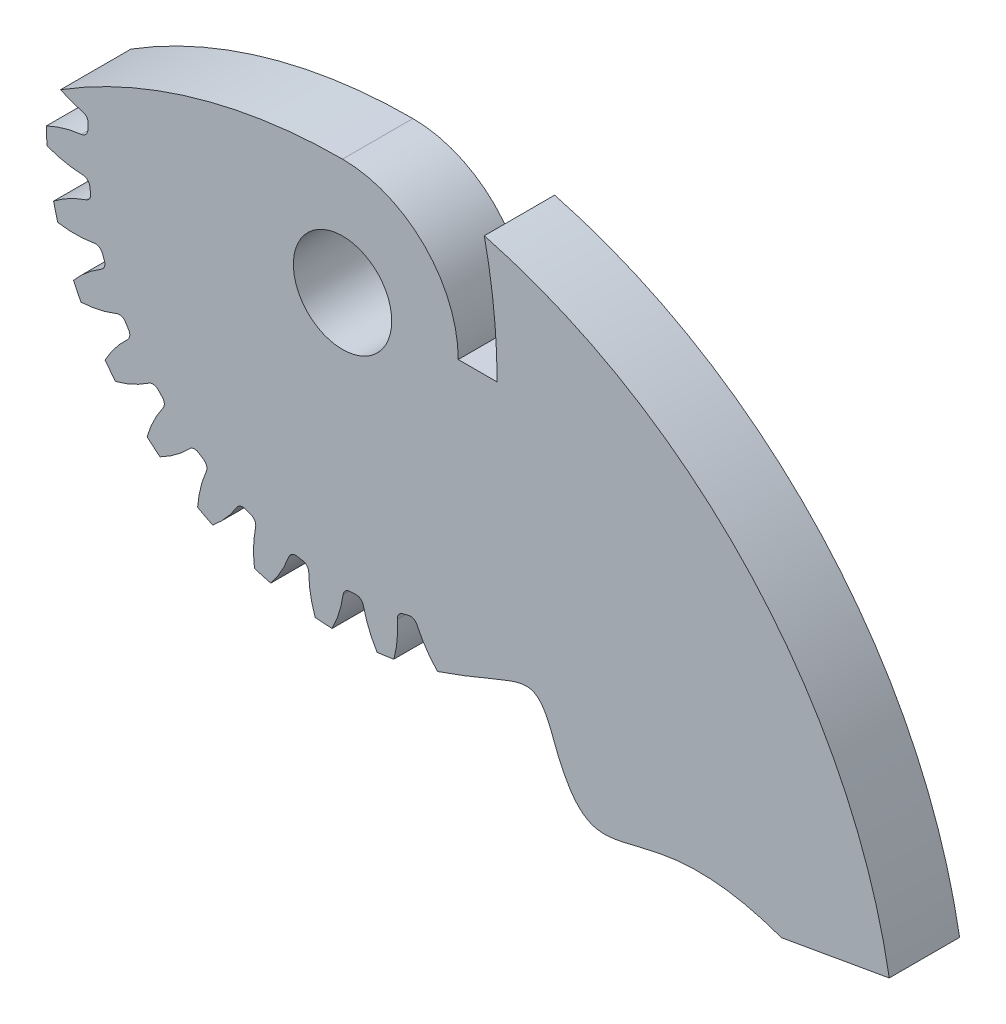
SolidWorks part; units mm, degrees
material "ABS"
ref_plane "Front" through (0, 0, 0) normal (0, 0, 1) x (1, 0, 0)
ref_plane "Top" through (0, 0, 0) normal (0, 1, 0) x (1, 0, 0)
ref_plane "Right" through (0, 0, 0) normal (1, 0, 0) x (0, 0, -1)
sketch "Sketch3" plane through (0, 0, 0) normal (0, 0, 1) x (1, 0, 0)
  circle A0 centre (0, 0) radius 40.64
  dimension "od" = 40.64
extrude "gearBody" add sketch "Sketch3" along normal blind 9.652
sketch "Sketch2" plane through (0, 0, 0) normal (0, 0, 1) x (1, 0, 0)
  line L0 (0, 0) -> (34.0786, 14.1158) construction
  line L1 (45.4751, -11.4855) -> (0, 0) construction
  line L2 (0, 0) -> (36.3143, 0) construction
  line L3 (38.0972, -0.458) -> (37.8451, -4.4001) construction
  line L5 (37.9712, -2.4291) -> (0, 0) construction
  line L7 (0, 0) -> (36.8864, 0) construction
  arc A0 (36.879, -0.7403) -> (36.6727, -3.9649) centre (0, 0) ccw construction
  arc A1 (40.637, 0.4947) -> (40.2427, -5.6687) centre (0, 0) ccw construction
  arc A2 (38.0972, -0.458) -> (37.8451, -4.4001) centre (0, 0) ccw construction
  arc A3 (34.9015, -2.6404) -> (34.9534, -1.8283) centre (0, 0) ccw
  arc A4 (45.4751, -11.4855) -> (35.6466, -3.6712) centre (32.0022, -18.3431) ccw
  arc A5 (45.4751, -11.4855) -> (46.5679, 5.5974) centre (0, 0) ccw
  arc A6 (46.5679, 5.5974) -> (35.8238, -0.9008) centre (34.0786, 14.1158) cw
  arc A7 (34.9534, -1.8283) -> (35.8238, -0.9008) centre (35.9376, -1.8798) cw
  arc A8 (35.6466, -3.6712) -> (34.9015, -2.6404) centre (35.8842, -2.7147) cw
  point P6 (46.5679, 5.5974)
  point P22 (45.4751, -11.4855)
  dimension "baseDia" = 73.7729
  dimension "od" = 81.28
  dimension "pd" = 76.2
  dimension "rd" = 70.0024
  dimension "rFillet" = 0.9855
  dimension "pointX" = 46.5679
  dimension "pointY" = 5.5974
  dimension "CTT" = 3.9421
  dimension "flankCenterAngle" = 22.5
extrude "toothCut" cut sketch "Sketch2" along normal through all
pattern_circular "CirPattern1" count 30 over 360 about axis through (0, 0, 9.652) along (0, 0, -1) of "toothCut"
sketch "hub1Dia" plane through (0, 0, 0) normal (0, 0, -1) x (-1, 0, 0)
  circle A0 centre (0, 0) radius 12.7
  dimension "hub1Dia" = 25.4
sketch "hub2Dia" plane through (0, 0, 9.652) normal (0, 0, 1) x (1, 0, 0)
  circle A0 centre (0, 0) radius 12.7
  dimension "hub2dia" = 25.4
sketch "boreDia" plane through (0, 0, 0) normal (0, 0, 1) x (1, 0, 0)
  circle A0 centre (0, 0) radius 6.7469
  dimension "boreDia" = 13.4937
extrude "bore" cut sketch "boreDia" against normal mid plane 25400
sketch "Sketch4" plane through (0, 0, 9.652) normal (0, 0, 1) x (1, 0, 0)
  circle A0 centre (0, -57.15) radius 76.1746
  arc A2 (-41.7195, 6.5842) -> (41.7195, 6.5842) centre (0, 0) cw
  dimension "D1" = 152.3492
  dimension "D2" = 57.15
extrude "Cut-Extrude1" cut sketch "Sketch4" against normal through all contours A0 region at (0, 26.0638, 9.652)
sketch "Sketch5" plane through (0, 0, 9.652) normal (0, 0, 1) x (1, 0, 0)
  line L0 (0, 19.0246) -> (21.5163, 3.7176)
  line L1 (21.5163, 3.7176) -> (8.9608, -26.928)
  line L2 (8.9608, -26.928) -> (13.028, -38.4952)
  line L3 (0, 0) -> (0, -57.15) construction
  line L4 (0, -57.15) -> (-54.1615, -3.586) construction
  line L5 (0, -57.15) -> (65.9691, -95.2373) construction
  line L9 (0, -57.15) -> (75.0173, -43.9224) construction
  line L12 (60.232, -46.5295) -> (75.0173, -43.9224)
  line L13 (0, -57.15) -> (29.696, -40.005) construction
  line L14 (29.696, -40.005) -> (26.521, -34.5057) construction
  circle A1 centre (0, -57.15) radius 76.1746 construction
  arc A5 (0, 19.0246) -> (75.0173, -43.9224) centre (0, -57.15) cw
  circle A6 centre (0, -57.15) radius 21.59 construction
  circle A12 centre (49.4934, -85.725) radius 40.64 construction
  spline S0 degree 3 poles (13.028, -38.4952) (20.557, -35.948) (26.6517, -31.726) (34.6651, -56.7545) (39.5345, -39.0169) (60.232, -46.5295) knots 0 0 0 0 0.118515 0.218515 1 1 1 1
  point P28 (21.569, -56.1981)
  dimension "D1" = 43.18
  dimension "D3" = 81.28
  dimension "D6" = 152.3492
  dimension "D2" = 120
  dimension "D4" = 57.15
  dimension "D8" = 57.15
  dimension "D7" = 60
  dimension "D9" = 34.29
  dimension "D10" = 6.35
  dimension "D5" = 80
extrude "Boss-Extrude1" add sketch "Sketch5" against normal up to surface (9.652 mm away) up to face at (6.7469, 0, 0)
sketch "Sketch6" plane through (0, 0, 9.652) normal (0, 0, 1) x (1, 0, 0)
  line L1 (-41.2993, 3.0747) -> (-42.3397, 6.1739)
  line L2 (15.875, 0) -> (21.209, 0)
  circle A0 centre (0, -57.15) radius 76.1746 construction
  arc A1 (75.0173, -43.9224) -> (-34.0662, 10.9827) centre (0, -57.15) ccw construction
  circle A2 centre (0, 0) radius 15.875 construction
  arc A3 (0, 15.875) -> (15.875, 0) centre (0, 0) cw
  arc A4 (19.4523, 16.499) -> (-42.3397, 6.1739) centre (0, -57.15) ccw
  arc A5 (0, 15.875) -> (-41.2993, 3.0747) centre (0, -57.15) ccw
  circle A6 centre (0, 0) radius 21.209 construction
  circle A8 centre (-57.15, 0) radius 78.359 construction
  arc A9 (21.209, 0) -> (19.4523, 16.499) centre (-57.15, 0) ccw
  dimension "D4" = 57.15
  dimension "D1" = 31.75
  dimension "D2" = 42.418
  dimension "D3" = 156.718
extrude "Cut-Extrude2" cut sketch "Sketch6" against normal through all
equation "\"Bodytube_OD\" = 6.17in"
equation "\"Bodytube_ID\" = 5.998in"
equation "\"Fwd_Tube_Length\" = 40in"
equation "\"Mid_Tube_Length\" = 1in"
equation "\"Aft_Section_Length\"= 39in"
equation "\"Mid_Coupler_Length\"= 13in"
equation "\"Aft_Lower_Length\"= 22in"
equation "\"AB_Coupler_OD_Length\"= 1in"
equation "\"AB_Coupling_Section_Length\"= 0.375in"
equation "\"AB_Coupler_Length\"= \"AB_Coupler_OD_Length\" + \"AB_Coupling_Section_Length\" * 2"
equation "\"Cutout_Angle\" = 80"
equation "\"AB_Paddle_Height\" = 0.375in"
equation "\"AB_Coupler_Num_Screws\"= 4"
equation "\"Num_Cutouts\" = 3"
equation "\"AB_Coupler_OD\"= 6.17in"
equation "\"AB_Coupler_ID\"= 5.75in"
equation "\"AB_Coupler_Surface_Diameter\"= 5.998in"
equation "\"AB_Coupling_Screw_Diameter\"= 0.15748in"
equation "\"AB_Central_Bushing_Length\" = .4724in"
equation "\"Lead_Screw_Dist\" = 3.4in"
equation "\"Lead_Screw_Diam\" = 0.386in"
equation "\"Lead_Screw_Length\" = (\"Mid_Coupler_Length\" + 2*0.375in + 2*0.5in)"
equation "\"Paddle_Pin_Offset\" = .25in"
equation "\"Paddle_Pin_Radius\" = 2.25in"
equation "\"Fwd_BKHD_From_Top\" = 18in"
equation "\"D1@Sketch4\"=\"Bodytube_ID\""
equation "\"D2@Sketch4\"=\"Paddle_Pin_Radius\""
equation "\"D3@Sketch5\"=\"Paddle_Gear_OD\""
equation "\"D4@Sketch5\"=\"Paddle_Pin_Radius\""
equation "\"Motor_OD\" = 4in"
equation "\"Aft_Upper_Length\"= \"Aft_Section_Length\" - \"Aft_Lower_Length\" - \"AB_Coupler_OD_Length\""
equation "\"Paddle_Gear_OD\" = 3.2in"
equation "\"D5@Sketch5\"=\"Cutout_Angle\""
equation "\"D6@Sketch5\"=\"Bodytube_ID\""
equation "\"D1@Sketch6\"=\"AB_Coupler_ID\"-2*\"Paddle_Pin_Radius\""
equation "\"D2@Sketch6\"=\"Bodytube_OD\"-2*\"Paddle_Pin_Radius\""
equation "\"D3@Sketch6\"=\"Bodytube_OD\""
equation "\"D4@Sketch6\"=\"Paddle_Pin_Radius\""
equation "\"D8@Sketch5\"=\"Paddle_Pin_Radius\""
equation "\"Drive_Gear_OD\" = 1.7in"
equation "\"Fin_Thickness\"= .118in"
equation "\"Guiderail_Cutout_Diameter\"= 1.5in"
equation "\"DB9_Hole_Dist\" = 25mm"
equation "\"D1@Sketch5\"=\"Drive_Gear_OD\""
